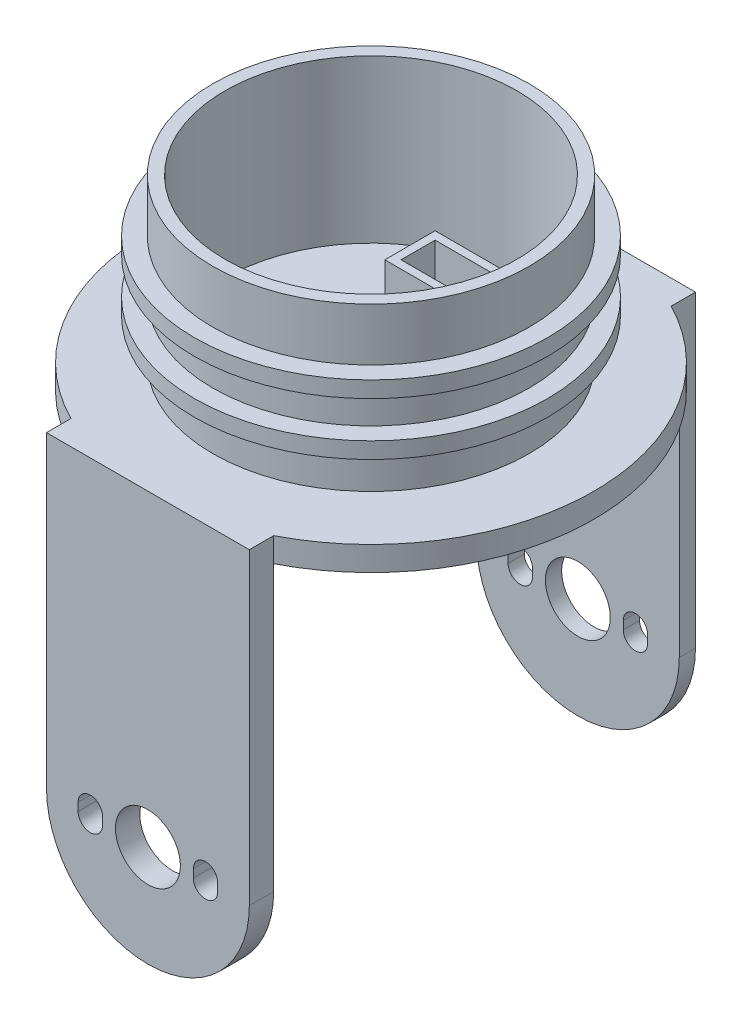
SolidWorks part; units mm, degrees
ref_plane "前基準面" through (0, 0, 0) normal (0, 0, 1) x (1, 0, 0)
ref_plane "上基準面" through (0, 0, 0) normal (0, 1, 0) x (1, 0, 0)
ref_plane "右基準面" through (0, 0, 0) normal (1, 0, 0) x (0, 0, -1)
sketch "草圖1" plane through (0, 0, 0) normal (0, 1, 0) x (1, 0, 0)
  circle A0 centre (0, 0) radius 19.5
  circle A1 centre (0, 0) radius 18
  dimension "D1" = 39
  dimension "D2" = 36
extrude "填料-伸長1" add sketch "草圖1" along normal blind 20
sketch "草圖3" plane through (0, 0, 0) normal (0, -1, 0) x (1, 0, 0)
  circle A0 centre (0, 0) radius 27.5
  dimension "D1" = 55
extrude "填料-伸長2" add sketch "草圖3" along normal blind 3
ref_plane "平面2" through (0, -3, 0) normal (0, -1, 0) x (-1, 0, 0)
ref_plane "平面5" through (0, 0, 0) normal (0, 1, 0) x (1, 0, 0)
ref_plane "平面6" through (0, 7, 0) normal (0, -1, 0) x (-1, 0, 0)
sketch "草圖25" plane through (0, 7, 0) normal (0, -1, 0) x (-1, 0, 0)
  circle A0 centre (0, 0) radius 21.75
  circle A1 centre (0, 0) radius 19.5
  dimension "D1" = 43.5
extrude "填料-伸長12" add sketch "草圖25" along normal blind 2
ref_plane "平面10" through (0, 10.5, 0) normal (0, -1, 0) x (-1, 0, 0)
sketch "草圖26" plane through (0, 10.5, 0) normal (0, -1, 0) x (-1, 0, 0)
  circle A0 centre (0, 0) radius 21.75
  circle A1 centre (0, 0) radius 19.5
extrude "填料-伸長13" add sketch "草圖26" against normal blind 2 from offset 1 offset against normal yes
sketch "草圖27" plane through (0, -3, 0) normal (0, -1, 0) x (1, 0, 0)
  line L0 (0, 0) -> (-12.5, 0)
  line L1 (46.0389, 0) -> (-46.0389, 0) construction
  line L2 (-12.5, 0) -> (-12.5, 25.5)
  line L3 (-12.5, 25.5) -> (12.5, 25.5)
  line L4 (12.5, 25.5) -> (12.5, 0)
  line L5 (12.5, 0) -> (-12.5, 0)
  line L6 (-12.5, 0) -> (-12.5, -25.5)
  line L7 (-12.5, -25.5) -> (12.5, -25.5)
  line L8 (12.5, -25.5) -> (12.5, 0)
  circle M6 centre (0, 0) radius 27.5
extrude "填料-伸長14" add sketch "草圖27" against normal blind 3 contours L8 L5 L0 L6 L7 M6 | L5 L4 L3 L2 L0 M6 | L6 L7 M6 | L7 L8 M6 | L4 L3 M6 | L3 L2 M6 region at (0, -3, -12.7084) region at (0, -3, 12.7084) region at (-11.7799, -3, 25.1714) region at (-11.7799, -3, -25.1714) region at (11.7799, -3, 25.1714) region at (11.7799, -3, -25.1714)
sketch "草圖28" plane through (0, 0, -25.5) normal (0, 0, -1) x (-1, 0, 0)
  line L0 (12.5, -3) -> (12.5, -38)
  line L1 (12.5, -38) -> (-12.5, -38)
  line L2 (-12.5, -38) -> (-12.5, 0)
  line L3 (-12.5, 0) -> (12.5, 0)
  line L4 (12.5, 0) -> (12.5, -3) construction
  line L5 (12.5, 0) -> (12.5, -3)
  line L6 (-7.1, -37.5) -> (-7.1, -38.5) construction
  line L7 (-5.6, -37.5) -> (-5.6, -38.5)
  line L8 (-8.6, -37.5) -> (-8.6, -38.5)
  line L9 (12.5, -3) -> (-12.5, -3)
  line L10 (7.1, -37.5) -> (7.1, -38.5) construction
  line L11 (8.6, -37.5) -> (8.6, -38.5)
  line L12 (5.6, -37.5) -> (5.6, -38.5)
  arc A0 (12.5, -38) -> (-12.5, -38) centre (0, -38) cw
  circle A1 centre (0, -38) radius 4
  arc A2 (-5.6, -37.5) -> (-8.6, -37.5) centre (-7.1, -37.5) ccw
  arc A3 (-8.6, -38.5) -> (-5.6, -38.5) centre (-7.1, -38.5) ccw
  arc A4 (8.6, -37.5) -> (5.6, -37.5) centre (7.1, -37.5) ccw
  arc A5 (5.6, -38.5) -> (8.6, -38.5) centre (7.1, -38.5) ccw
  point P14 (-7.1, -38)
  point P19 (-7.1, -36)
  point P20 (-7.1, -40)
  point P26 (7.1, -38)
  point P31 (7.1, -36)
  point P32 (7.1, -40)
  line M17 (10.2956, 0) -> (10.2956, -3)
  line M18 (10.2956, -3) -> (12.5, -3)
  line M19 (12.5, -3) -> (12.5, 0)
  line M20 (12.5, 0) -> (10.2956, 0)
  dimension "D1" = 8
  dimension "D2" = 4
  dimension "D3" = 3
  dimension "D4" = 5.6
  dimension "D5" = 4
  dimension "D6" = 3
  dimension "D7" = 5.6
  dimension "D8" = 35
extrude "填料-伸長17" add sketch "草圖28" along normal blind 2 contours A4 L11 L1 L0 L9 L2 L8 A2 L7 A1 L12 M18 | L9 L3 L2 M17 | M20 M17 M18 M19 | A5 L12 L1 A1 L7 A3 L8 A0 L11 region at (-11.3978, -1.5, -25.5) region at (0, -19.8277, -25.5) region at (0, -43.9487, -25.5) region at (1.1022, -1.5, -25.5)
extrude "填料-伸長19" add sketch "草圖28<15>" against normal blind 53 contours A4 L11 L1 L0 L9 L2 L8 A2 L7 A1 L12 M18 | A5 L12 L1 A1 L7 A3 L8 A0 L11 region at (0, -19.8277, -25.5) region at (0, -43.9487, -25.5)
sketch "草圖28<15>" plane through (0, 0, -25.5) normal (0, 0, -1) x (-1, 0, 0) same geometry as "草圖28"
sketch "草圖32" plane through (0, 0, 25.5) normal (0, 0, 1) x (1, 0, 0)
  line L0 (10.2956, -3) -> (12.5, -3)
  line L1 (-30.25, -3) -> (30.25, -3) construction
  line L2 (12.5, -3) -> (0, -3) construction
  line L3 (12.5, -3) -> (12.5, 0)
  line L4 (19.5, 0) -> (-19.5, 0) construction
  line L5 (12.5, 0) -> (12.5, -3) construction
  line L6 (12.5, 0) -> (10.2956, 0)
  line L7 (10.2956, 0) -> (10.2956, -3) construction
  line L8 (10.2956, 0) -> (10.2956, -3)
  line L9 (-10.2956, 0) -> (-10.2956, -3)
  line L10 (-10.2956, -3) -> (-10.2956, 0) construction
  line L11 (0, -3) -> (-12.5, -3) construction
  line L12 (-12.5, -3) -> (-10.2956, -3) construction
  line L13 (-10.2956, -3) -> (-12.5, -3)
  line L14 (-12.5, -3) -> (-12.5, 0)
  line L15 (-12.5, -3) -> (-12.5, 0) construction
  line L16 (-12.5, 0) -> (-10.2956, 0)
extrude "填料-伸長20" add sketch "草圖32" along normal blind 2
extrude "除料-伸長8" cut sketch "草圖28<18>" against normal blind 50 contours A4 L11 L1 L0 L9 L2 L8 A2 L7 A1 L12 M18 | A5 L12 L1 A1 L7 A3 L8 A0 L11 region at (0, -19.8277, -25.5) region at (0, -43.9487, -25.5)
sketch "草圖28<18>" plane through (0, 0, -25.5) normal (0, 0, -1) x (-1, 0, 0) same geometry as "草圖28"
sketch "草圖33" plane through (0, 0, 27.5) normal (0, 0, 1) x (1, 0, 0)
  line L0 (-12.5, -3) -> (12.5, -3)
  line L1 (-30.25, -3) -> (30.25, -3) construction
  line L2 (-12.5, -3) -> (-12.5, 0) construction
  line L3 (12.5, 0) -> (12.5, -3) construction
  line L4 (12.5, -3) -> (12.5, 0)
  line L5 (19.5, 0) -> (-19.5, 0) construction
  line L6 (12.5, 0) -> (-12.5, 0)
  line L7 (-12.5, 0) -> (-12.5, -3)
extrude "填料-伸長21" add sketch "草圖33" against normal blind 3
sketch "草圖34" plane through (0, 0, 0) normal (0, 1, 0) x (1, 0, 0)
  line L0 (0, 0) -> (-17.3838, 0) construction
  line L1 (-17.3838, 0) -> (19.1481, 0) construction
  line L2 (0, 0) -> (0, -21.2728) construction
  line L3 (0, -21.2728) -> (0, 19.1859) construction
  line L4 (5.1, 13) -> (-5.1, 13) construction
  line L5 (-4.1, 12) -> (4.1, 12)
  line L6 (-4.1, 12) -> (-4.1, 7.8)
  line L7 (-4.1, 7.8) -> (4.1, 7.8)
  line L8 (4.1, 12) -> (4.1, 7.8)
  line L10 (5.1, 6.8) -> (-5.1, 6.8)
  line L11 (5.1, 6.8) -> (5.1, 13)
  line L12 (5.1, 13) -> (-5.1, 13)
  line L13 (-5.1, 6.8) -> (-5.1, 13)
  point P13 (0, 13)
  dimension "D1" = 8.2
  dimension "D2" = 4.2
  dimension "D3" = 1
  dimension "D4" = 12
  dimension "D5" = 1
  dimension "D6" = 1
  dimension "D7" = 1
extrude "填料-伸長22" add sketch "草圖34" along normal blind 5
sketch "草圖37" plane through (0, 0, 0) normal (0, 1, 0) x (1, 0, 0)
  line L2 (-4.1, 12) -> (4.1, 12)
  line L3 (-4.1, 12) -> (-4.1, 7.8)
  line L4 (-4.1, 7.8) -> (4.1, 7.8)
  line L5 (4.1, 12) -> (4.1, 7.8)
extrude "除料-伸長9" cut sketch "草圖37" against normal blind 5
